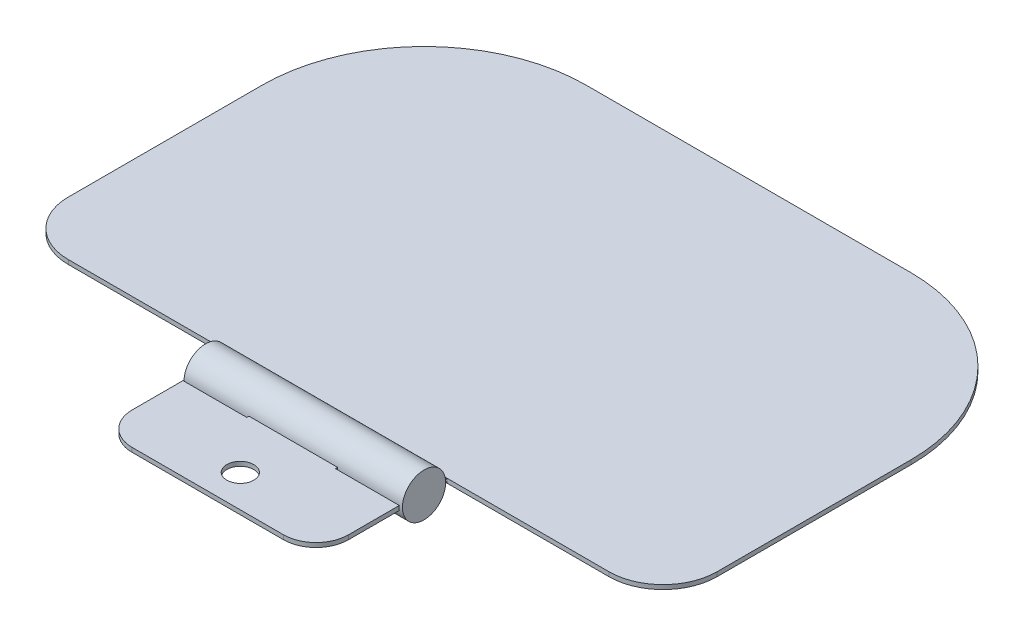
SolidWorks part; units mm, degrees
ref_plane "前视基准面" through (0, 0, 0) normal (0, 0, 1) x (1, 0, 0)
ref_plane "上视基准面" through (0, 0, 0) normal (0, 1, 0) x (1, 0, 0)
ref_plane "右视基准面" through (0, 0, 0) normal (1, 0, 0) x (0, 0, -1)
sketch "草图2" plane through (0, 0, 0) normal (0, 1, 0) x (1, 0, 0)
  line L0 (-23.7913, 37.5761) -> (-8.7913, 37.5761)
  line L1 (31.2087, 42.5761) -> (31.2087, 60.4856)
  line L2 (-28.7913, 60.4856) -> (-28.7913, 42.5761)
  line L3 (-13.7913, 75.4856) -> (16.2087, 75.4856)
  line L4 (-8.7913, 37.5761) -> (-8.7913, 28.4856)
  line L5 (11.2087, 37.5761) -> (11.2087, 28.4856)
  line L6 (-5.7913, 25.4856) -> (8.2087, 25.4856)
  line L7 (11.2087, 37.5761) -> (26.2087, 37.5761)
  arc A0 (-13.7913, 75.4856) -> (-28.7913, 60.4856) centre (-13.7959, 60.4902) ccw
  arc A1 (31.2087, 60.4856) -> (16.2087, 75.4856) centre (16.2087, 60.4856) ccw
  arc A2 (-8.7913, 28.4856) -> (-5.7913, 25.4856) centre (-5.7913, 28.4856) ccw
  arc A3 (8.2087, 25.4856) -> (11.2087, 28.4856) centre (8.2087, 28.4856) ccw
  arc A4 (-28.7913, 42.5761) -> (-23.7913, 37.5761) centre (-23.7913, 42.5761) ccw
  arc A5 (26.2087, 37.5761) -> (31.2087, 42.5761) centre (26.2087, 42.5761) ccw
  circle A6 centre (1.2087, 28.4856) radius 1.25
extrude "凸台-拉伸1" add sketch "草图2" along normal blind 0.2 and the other way blind 0.2
sketch "草图4" plane through (11.2087, 0, 0) normal (1, 0, 0) x (0, 0, -1)
  line L0 (37.5761, -0.2) -> (37.5761, 0.2) construction
  circle A0 centre (35.3761, 0) radius 2
  point P2 (37.5761, 0)
  dimension "D1" = 2.2
extrude "凸台-拉伸3" add sketch "草图4" along normal blind 0.1 and the other way blind 20.1
sketch "草图6" plane through (-8.8913, 0, 0) normal (-1, 0, 0) x (0, 0, 1)
  circle A0 centre (-35.3761, 0) radius 2
  circle A1 centre (-35.3761, 0) radius 2.2
extrude "切除-拉伸2" cut sketch "草图6" against normal blind 6
sketch "草图7" plane through (11.3087, 0, 0) normal (1, 0, 0) x (0, 0, -1)
  circle A0 centre (35.3761, 0) radius 2
  circle A1 centre (35.3761, 0) radius 2.2
extrude "切除-拉伸3" cut sketch "草图7" against normal blind 6
